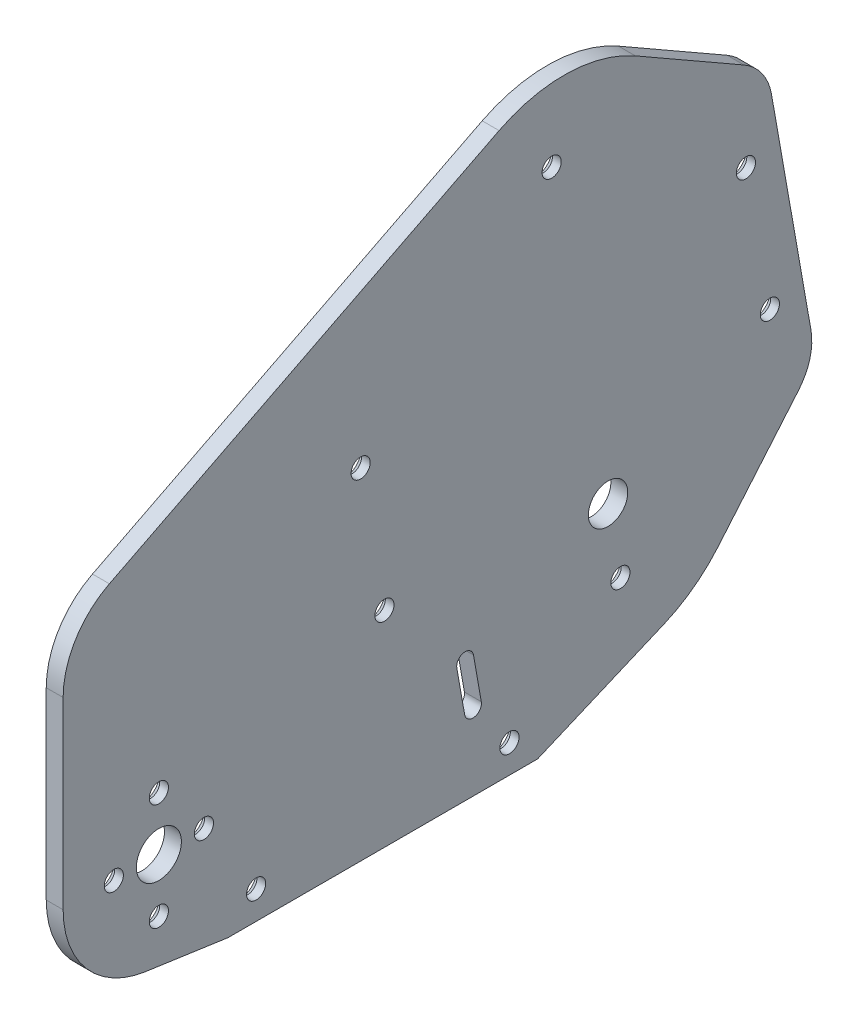
SolidWorks part; units mm, degrees
material "Thornel VCB-20 Carbon Cloth"
ref_plane "Front Plane" through (0, 0, 0) normal (0, 0, 1) x (1, 0, 0)
ref_plane "Top Plane" through (0, 0, 0) normal (0, 1, 0) x (1, 0, 0)
ref_plane "Right Plane" through (0, 0, 0) normal (1, 0, 0) x (0, 0, -1)
ref_plane "Plane1" through (-20, 0, 0) normal (-1, 0, 0) x (0, 0, 1)
sketch "Sketch2" plane through (-20, 0, 0) normal (-1, 0, 0) x (0, 0, 1)
  line L21 (-20.652, 137.0588) -> (48.554, 101.9611)
  line L33 (-73.8247, 70.5164) -> (-59.4754, 53.5392)
  line L34 (-69.0263, 118.4582) -> (-76.0353, 78.7081)
  line L35 (-44.8568, 136.4454) -> (-64.1472, 125.3998)
  line L36 (16.6915, 108.8163) -> (-16.6101, 134.5066)
  line L37 (44.3742, 103.3553) -> (18.8773, 107.8511)
  line L38 (56.7694, 55.9345) -> (56.7694, 88.5832)
  line L39 (27.5, 37) -> (42.1838, 39.1068)
  line L40 (-27.5, 37) -> (27.5, 37)
  line L41 (-49.9564, 46.5241) -> (-27.5, 37)
  line L42 (-73.8247, 70.5164) -> (-59.4754, 53.5392)
  line L43 (-69.0263, 118.4582) -> (-76.0353, 78.7081)
  line L44 (-44.8568, 136.4454) -> (-64.1472, 125.3998)
  line L47 (56.7694, 55.9345) -> (56.7694, 88.5832)
  line L48 (27.5, 37) -> (42.1838, 39.1068)
  line L49 (-27.5, 37) -> (27.5, 37)
  line L50 (-49.9564, 46.5241) -> (-27.5, 37)
  arc A22 (-76.0353, 78.7081) -> (-73.8247, 70.5164) centre (-66.1872, 76.9716) ccw
  arc A23 (-64.1472, 125.3998) -> (-69.0263, 118.4582) centre (-59.1782, 116.7217) ccw
  arc A24 (-16.6101, 134.5066) -> (-44.8568, 136.4454) centre (-32.1858, 114.3163) ccw
  arc A25 (16.6915, 108.8163) -> (18.8773, 107.8511) centre (19.7456, 112.7751) ccw
  arc A26 (56.7694, 88.5832) -> (44.3742, 103.3553) centre (41.7694, 88.5832) ccw
  arc A27 (42.1838, 39.1068) -> (56.7694, 55.9345) centre (39.7694, 55.9345) ccw
  arc A28 (-59.4754, 53.5392) -> (-49.9564, 46.5241) centre (-40, 70) ccw
  arc A29 (-76.0353, 78.7081) -> (-73.8247, 70.5164) centre (-66.1872, 76.9716) ccw
  arc A30 (-64.1472, 125.3998) -> (-69.0263, 118.4582) centre (-59.1782, 116.7217) ccw
  arc A31 (-20.652, 137.0588) -> (-44.8568, 136.4454) centre (-32.1858, 114.3163) ccw
  arc A33 (56.7694, 88.5832) -> (48.554, 101.9611) centre (41.7694, 88.5832) ccw
  arc A34 (42.1838, 39.1068) -> (56.7694, 55.9345) centre (39.7694, 55.9345) ccw
  arc A35 (-59.4754, 53.5392) -> (-49.9564, 46.5241) centre (-40, 70) ccw
  dimension "D1" = 0
extrude "Boss-Extrude1" add sketch "Sketch2" along normal blind 3 contours L42 A35 L50 L49 L48 A34 L47 A33 L21 A31 L44 A30 L43 A29 region at (-20, 115.6734, 15.2446) region at (-20, 82.3149, -11.2073)
sketch "Sketch7" plane through (0, 0, 0) normal (1, 0, 0) x (0, 0, -1)
  line L0 (-49.2694, 55.9345) -> (-30.2694, 55.9345)
  line L1 (-39.7694, 65.4345) -> (-49.2694, 55.9345)
  line L2 (-49.2694, 55.9345) -> (-39.7694, 46.4345)
  line L3 (-39.7694, 46.4345) -> (-30.2694, 55.9345)
  line L4 (-30.2694, 55.9345) -> (-39.7694, 65.4345)
  circle A0 centre (-39.7694, 55.9345) radius 14 construction
  circle A1 centre (-39.7694, 55.9345) radius 14 construction
  circle A2 centre (-39.7694, 55.9345) radius 9.5 construction
  circle A3 centre (-39.7694, 55.9345) radius 6.7175 construction
  circle A4 centre (-39.7694, 55.9345) radius 8 construction
  point P10 (-47.7694, 55.9345)
  point P11 (-31.7694, 55.9345)
  dimension "D1" = 19
  dimension "D2" = 16
hole_wizard "CSK for M3 Flat Head Machine Screw1" positions "Sketch3" profile "Sketch4" countersink size "M3" standard "ANSI Metric" end condition through all
sketch "Sketch3" plane through (-23, 0, 0) normal (-1, 0, 0) x (0, 0, 1)
  point P0 (-64.4907, 109.4197)
  point P2 (-68.7373, 85.5447)
  point P5 (-29.9892, 126.7742)
  point P8 (-42.1966, 57.5422)
  point P11 (-0.2931, 73.4761)
  point P14 (3.9375, 97.4693)
  point P17 (22.5, 42)
  point P20 (-22.5, 42)
  point P24 (39.7694, 65.4345)
  point P30 (39.7694, 46.4345)
  point P39 (31.7694, 55.9345)
  point P42 (47.7694, 55.9345)
sketch "Sketch4" plane through (-23, 109.4197, -64.4907) normal (0, 1, 0) x (0, 0, 1)
  line L0 (0, 0) -> (0, 3)
  line L1 (0, 3) -> (1.7, 3)
  line L2 (1.7, 3) -> (1.7, 1.45)
  line L3 (1.7, 1.45) -> (3.15, 0)
  line L5 (3.15, 0) -> (0, 0)
  line L6 (-1.7, 1.45) -> (-3.15, 0) construction
  line L11 (0, -6.35) -> (0, 107.95) construction
  dimension "Thru Hole Dia." = 3.4
  dimension "Thru Hole Depth" = 3
  dimension "Near C'Sink Dia." = 6.3
  dimension "Near C'Sink Angle" = 90
hole_wizard "Hole1" positions "Sketch5" profile "Sketch6" legacy end condition through all
sketch "Sketch5" plane through (-23, 0, 0) normal (-1, 0, 0) x (0, 0, 1)
  point P0 (-40, 70)
sketch "Sketch6" plane through (-23, 70, -40) normal (0, 1, 0) x (0, 0, 1)
  line L0 (0, 0) -> (0, 3)
  line L1 (0, 3) -> (3.5, 3)
  line L2 (3.5, 3) -> (3.5, 0)
  line L3 (3.5, 0) -> (0, 0)
  line L4 (0, 110) -> (0, -10) construction
  dimension "Diameter" = 7
  dimension "Depth" = 3
hole_wizard "Hole2" positions "Sketch8" profile "Sketch9" legacy end condition through all
sketch "Sketch8" plane through (-23, 0, 0) normal (-1, 0, 0) x (0, 0, 1)
  point P0 (39.7694, 55.9345)
sketch "Sketch9" plane through (-23, 55.9345, 39.7694) normal (0, 1, 0) x (0, 0, 1)
  line L0 (0, 0) -> (0, 3)
  line L1 (0, 3) -> (4, 3)
  line L2 (4, 3) -> (4, 0)
  line L3 (4, 0) -> (0, 0)
  line L4 (0, 110) -> (0, -10) construction
  dimension "Diameter" = 8
  dimension "Depth" = 3
sketch "Sketch10" plane through (-23, 0, 0) normal (-1, 0, 0) x (0, 0, 1)
  line L0 (-40, 70) -> (39.7694, 55.9345) construction
  line L1 (-40, 70) -> (39.7694, 55.9345) construction
  line L2 (-38.7845, 76.8937) -> (40.985, 62.8282) construction
  line L3 (-41.2155, 63.1063) -> (38.5539, 49.0408) construction
  line L4 (-14.6257, 58.4178) -> (-16.0149, 50.5394) construction
  line L5 (-10.6865, 57.7233) -> (-12.0757, 49.8448) construction
  line L6 (-18.565, 59.1124) -> (-19.9541, 51.234) construction
  line L8 (-16.0149, 50.5394) -> (-14.6257, 58.4178) construction
  line L9 (-17.4921, 50.7999) -> (-16.1029, 58.6783)
  line L10 (-14.5377, 50.2789) -> (-13.1485, 58.1574)
  arc A0 (-38.7845, 76.8937) -> (-41.2155, 63.1063) centre (-40, 70) ccw construction
  arc A1 (38.5539, 49.0408) -> (40.985, 62.8282) centre (39.7694, 55.9345) ccw construction
  arc A2 (-10.6865, 57.7233) -> (-18.565, 59.1124) centre (-14.6257, 58.4178) ccw construction
  arc A3 (-19.9541, 51.234) -> (-12.0757, 49.8448) centre (-16.0149, 50.5394) ccw construction
  arc A4 (-17.4921, 50.7999) -> (-14.5377, 50.2789) centre (-16.0149, 50.5394) ccw
  arc A5 (-13.1485, 58.1574) -> (-16.1029, 58.6783) centre (-14.6257, 58.4178) ccw
  point P4 (-0.1153, 62.9672)
  point P11 (-15.3203, 54.4786)
  point P20 (-15.3203, 54.4786)
  dimension "D1" = 4
  dimension "D4" = 1.5
  dimension "D2" = 14
  dimension "D3" = 8
  dimension "D5" = 27
extrude "Cut-Extrude1" cut sketch "Sketch10" against normal through all
